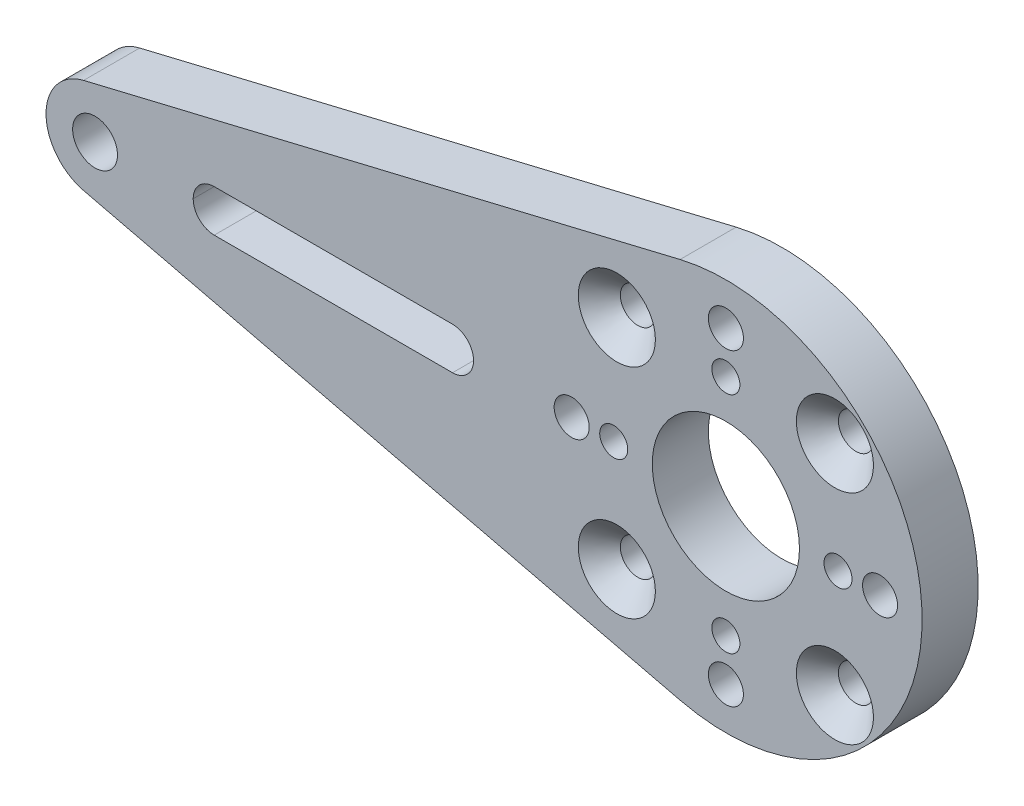
SolidWorks part; units mm, degrees
material "6061 Alloy"
ref_plane "Front Plane" through (0, 0, 0) normal (0, 0, 1) x (1, 0, 0)
ref_plane "Top Plane" through (0, 0, 0) normal (0, 1, 0) x (1, 0, 0)
ref_plane "Right Plane" through (0, 0, 0) normal (1, 0, 0) x (0, 0, -1)
sketch "Sketch1" plane through (0, 0, 0) normal (0, 0, 1) x (1, 0, 0)
  line L0 (-45.8167, 3.4034) -> (-3.2667, 13.6136)
  line L1 (-45.8167, -3.4034) -> (-3.2667, -13.6136)
  arc A0 (-3.2667, -13.6136) -> (-3.2667, 13.6136) centre (0, 0) ccw
  circle A1 centre (-45, 0) radius 1.6
  arc A2 (-45.8167, 3.4034) -> (-45.8167, -3.4034) centre (-45, 0) ccw
  circle A3 centre (0, 0) radius 5.25
  dimension "D1" = 28
  dimension "D2" = 3.2
  dimension "D3" = 7
  dimension "D4" = 10.5
  dimension "D5" = 45
extrude "Boss-Extrude1" add sketch "Sketch1" along normal blind 4
sketch "Sketch2" plane through (0, 0, 4) normal (0, 0, 1) x (1, 0, 0)
  circle A0 centre (0, 0) radius 8 construction
  circle A1 centre (0, 8) radius 1
  dimension "D1" = 16
  dimension "D2" = 2
extrude "Cut-Extrude1" cut sketch "Sketch2" against normal up to next
pattern_circular "CirPattern1" count 4 over 360 about axis through (0, 0, 4) along (0, 0, 1) of "Cut-Extrude1"
sketch "Sketch3" plane through (0, 0, 4) normal (0, 0, 1) x (1, 0, 0)
  circle A0 centre (0, 0) radius 11 construction
  circle A1 centre (0, 11) radius 1.25
  dimension "D1" = 22
  dimension "D2" = 2.5
extrude "Cut-Extrude2" cut sketch "Sketch3" against normal up to next
pattern_circular "CirPattern2" count 8 over 360 about axis through (0, 0, 4) along (0, 0, 1) of "Cut-Extrude2"
chamfer "Chamfer1" distance 1.5 angle 45 4 edges at (8.6621, 6.8943, 4) (6.8943, -8.6621, 4) (-8.6621, -6.8943, 4) (-6.8943, 8.6621, 4)
sketch "Sketch4" plane through (0, 0, 4) normal (0, 0, 1) x (1, 0, 0)
  line L0 (-45, 0) -> (-11, 0) construction
  line L2 (-18, -1.5) -> (-38, -1.5)
  line L3 (-18, -1.5) -> (-18, 1.5)
  line L4 (-18, 1.5) -> (-38, 1.5)
  line L5 (-38, -1.5) -> (-38, 1.5)
  line L6 (-18, -1.5) -> (-38, 1.5) construction
  line L7 (-18, 1.5) -> (-38, -1.5) construction
  point P4 (-28, 0)
  dimension "D1" = 3
  dimension "D2" = 20
extrude "Cut-Extrude3" cut sketch "Sketch4" against normal up to next
fillet "Fillet1" radius 1.5 4 edges at (-18, -1.5, 2) (-18, 1.5, 2) (-38, 1.5, 2) (-38, -1.5, 2)
